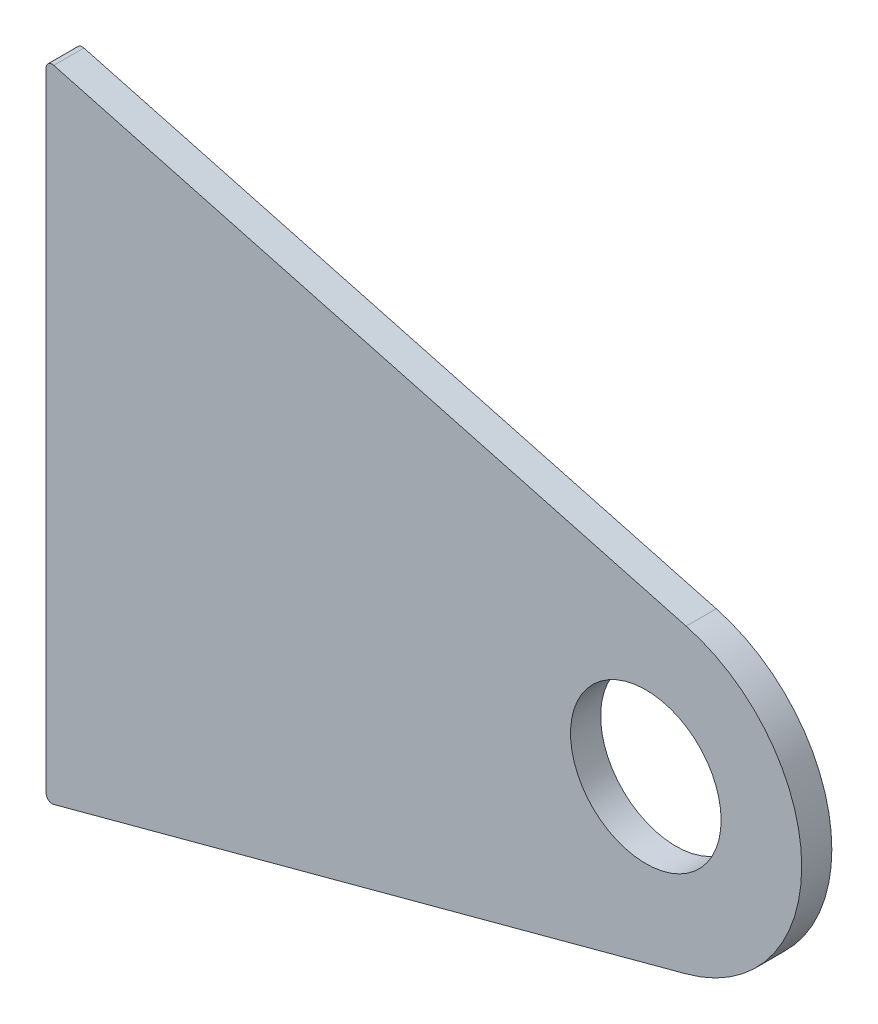
SolidWorks part; units mm, degrees
ref_plane "Front Plane" through (0, 0, 0) normal (0, 0, 1) x (1, 0, 0)
ref_plane "Top Plane" through (0, 0, 0) normal (0, 1, 0) x (1, 0, 0)
ref_plane "Right Plane" through (0, 0, 0) normal (1, 0, 0) x (0, 0, -1)
other "Configuration Table"
sketch "Sketch1" plane through (0, 0, 0) normal (0, 0, 1) x (1, 0, 0)
  line L0 (13.3975, -50) -> (-199.1062, -106.9402)
  line L1 (13.3975, 50) -> (-199.1062, 106.9402)
  line L2 (0, 0) -> (257.7333, 0) construction
  line L3 (-199.1062, 106.9402) -> (-199.1062, -106.9402)
  circle A0 centre (0, 0) radius 25
  arc A1 (13.3975, 50) -> (13.3975, -50) centre (0, 0) cw
  dimension "D1" = 50
  dimension "D2" = 30
  dimension "D4" = 50
  dimension "D5" = 50
  dimension "D6" = 220
  dimension "D7" = 220
  dimension "D3" = 199.1062
extrude "Boss-Extrude2" add sketch "Sketch1" along normal blind 10 contours L2 L3 L0 A1 A0 | L3 L2 A0 A1 L1 region at (-100.5697, 0, 0)
fillet "Fillet2" radius 2 2 edges at (-199.1062, -106.9402, 5) (-199.1062, 106.9402, 5)
ref_axis "Axis1" through (0, 0, 10) along (0, 0, -1)
equation "\"D4@Sketch1\" = \"D5@Sketch1\""
equation "\"D7@Sketch1\" = \"D6@Sketch1\""
